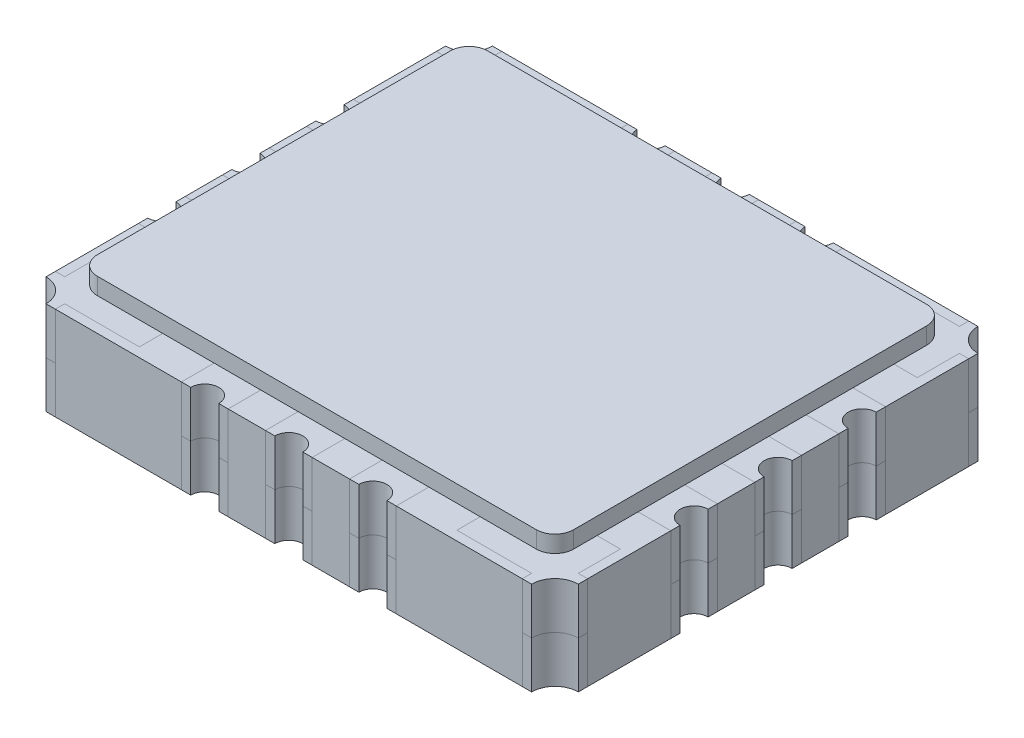
SolidWorks part; units mm, degrees
ref_plane "Спереди" through (0, 0, 0) normal (0, 0, 1) x (1, 0, 0)
ref_plane "Сверху" through (0, 0, 0) normal (0, 1, 0) x (1, 0, 0)
ref_plane "Справа" through (0, 0, 0) normal (1, 0, 0) x (0, 0, -1)
sketch "Эскиз1" plane through (0, 0, 0) normal (0, 1, 0) x (1, 0, 0)
  line L0 (0, 2.39) -> (0, -2.39) construction
  line L1 (-2.6, 2.39) -> (-1.05, 2.39)
  line L2 (-2.85, 2.14) -> (-2.85, 1.05)
  line L3 (-2.6, -2.39) -> (-1.05, -2.39)
  line L4 (2.85, 2.14) -> (2.85, 1.05)
  line L5 (-2.85, 0) -> (2.85, 0) construction
  line L6 (-2.85, -0.65) -> (-1.85, -0.65)
  line L7 (-2.85, 1.15) -> (-1.85, 1.15)
  line L8 (-2.85, 1.15) -> (-2.85, 1.05)
  line L9 (-2.85, 0.65) -> (-1.85, 0.65)
  line L10 (-1.85, 1.15) -> (-1.85, 0.65)
  line L11 (-2.85, 0.25) -> (-1.85, 0.25)
  line L12 (-2.85, 0.25) -> (-2.85, 0.15)
  line L13 (-2.85, -0.25) -> (-1.85, -0.25)
  line L14 (-1.85, 0.25) -> (-1.85, -0.25)
  line L15 (-2.85, -0.65) -> (-2.85, -0.75)
  line L16 (-2.85, -1.15) -> (-1.85, -1.15)
  line L17 (-1.85, -0.65) -> (-1.85, -1.15)
  line L18 (-0.75, -2.39) -> (-0.15, -2.39)
  line L19 (-0.75, -2.39) -> (-0.65, -2.39)
  line L20 (0.65, -2.39) -> (0.65, -1.39)
  line L21 (-1.15, -2.39) -> (-1.15, -1.39)
  line L22 (-1.15, -2.39) -> (-1.05, -2.39)
  line L23 (-0.65, -2.39) -> (-0.65, -1.39)
  line L24 (-1.15, -1.39) -> (-0.65, -1.39)
  line L25 (-0.25, -2.39) -> (-0.25, -1.39)
  line L26 (-0.25, -2.39) -> (-0.15, -2.39)
  line L27 (0.25, -2.39) -> (0.25, -1.39)
  line L28 (-0.25, -1.39) -> (0.25, -1.39)
  line L29 (0.65, -2.39) -> (0.75, -2.39)
  line L30 (1.15, -2.39) -> (1.15, -1.39)
  line L31 (0.65, -1.39) -> (1.15, -1.39)
  line L32 (0.15, -2.39) -> (0.75, -2.39)
  line L33 (0.15, -2.39) -> (0.25, -2.39)
  line L34 (1.05, -2.39) -> (1.15, -2.39)
  line L35 (1.05, -2.39) -> (2.6, -2.39)
  line L36 (-2.85, 0.75) -> (-2.85, 0.15)
  line L37 (-2.85, 0.75) -> (-2.85, 0.65)
  line L38 (-2.85, -0.15) -> (-2.85, -0.25)
  line L39 (-2.85, -0.15) -> (-2.85, -0.75)
  line L40 (-2.85, -1.05) -> (-2.85, -1.15)
  line L41 (-2.85, -1.05) -> (-2.85, -2.14)
  line L42 (-2.85, 0.75) -> (-2.85, 0.25)
  line L43 (-2.85, 0.25) -> (-2.8423, 0.2575)
  line L44 (2.85, 0.25) -> (2.8423, 0.2575)
  line L45 (2.85, 0.75) -> (2.85, 0.25)
  line L46 (2.85, -1.05) -> (2.85, -1.15)
  line L47 (2.85, -0.15) -> (2.85, -0.75)
  line L48 (2.85, -0.15) -> (2.85, -0.25)
  line L49 (2.85, 0.75) -> (2.85, 0.65)
  line L50 (2.85, 0.75) -> (2.85, 0.15)
  line L51 (1.85, -0.65) -> (1.85, -1.15)
  line L52 (2.85, -1.15) -> (1.85, -1.15)
  line L53 (2.85, -0.65) -> (2.85, -0.75)
  line L54 (1.85, 0.25) -> (1.85, -0.25)
  line L55 (2.85, -0.25) -> (1.85, -0.25)
  line L56 (2.85, 0.25) -> (2.85, 0.15)
  line L57 (2.85, 0.25) -> (1.85, 0.25)
  line L58 (1.85, 1.15) -> (1.85, 0.65)
  line L59 (2.85, 0.65) -> (1.85, 0.65)
  line L60 (2.85, 1.15) -> (2.85, 1.05)
  line L61 (2.85, 1.15) -> (1.85, 1.15)
  line L62 (2.85, -0.65) -> (1.85, -0.65)
  line L63 (1.05, 2.39) -> (1.15, 2.39)
  line L64 (0.15, 2.39) -> (0.25, 2.39)
  line L65 (0.15, 2.39) -> (0.75, 2.39)
  line L66 (0.65, 1.39) -> (1.15, 1.39)
  line L67 (1.15, 2.39) -> (1.15, 1.39)
  line L68 (0.65, 2.39) -> (0.75, 2.39)
  line L69 (-0.25, 1.39) -> (0.25, 1.39)
  line L70 (0.25, 2.39) -> (0.25, 1.39)
  line L71 (-0.25, 2.39) -> (-0.15, 2.39)
  line L72 (-0.25, 2.39) -> (-0.25, 1.39)
  line L73 (-1.15, 1.39) -> (-0.65, 1.39)
  line L74 (-0.65, 2.39) -> (-0.65, 1.39)
  line L75 (-1.15, 2.39) -> (-1.05, 2.39)
  line L76 (-1.15, 2.39) -> (-1.15, 1.39)
  line L77 (0.65, 2.39) -> (0.65, 1.39)
  line L78 (-0.75, 2.39) -> (-0.65, 2.39)
  line L79 (-0.75, 2.39) -> (-0.15, 2.39)
  line L80 (-2.5, 2.39) -> (-2.5, 2.29)
  line L81 (-2.5, 2.29) -> (-1.7, 2.29)
  line L82 (-2.75, 2.04) -> (-2.75, 1.59)
  line L83 (-2.75, 1.59) -> (-1.7, 1.59)
  line L84 (-1.7, 2.29) -> (-1.7, 1.59)
  line L85 (-2.85, 2.04) -> (-2.75, 2.04)
  line L86 (2.85, 2.04) -> (2.75, 2.04)
  line L87 (1.7, 2.29) -> (1.7, 1.59)
  line L88 (2.75, 1.59) -> (1.7, 1.59)
  line L89 (2.75, 2.04) -> (2.75, 1.59)
  line L90 (2.5, 2.29) -> (1.7, 2.29)
  line L91 (2.5, 2.39) -> (2.5, 2.29)
  line L92 (2.5, -2.39) -> (2.5, -2.29)
  line L93 (2.5, -2.29) -> (1.7, -2.29)
  line L94 (2.75, -2.04) -> (2.75, -1.59)
  line L95 (2.75, -1.59) -> (1.7, -1.59)
  line L96 (1.7, -2.29) -> (1.7, -1.59)
  line L97 (2.85, -2.04) -> (2.75, -2.04)
  line L98 (-2.85, -2.04) -> (-2.75, -2.04)
  line L99 (-1.7, -2.29) -> (-1.7, -1.59)
  line L100 (-2.75, -1.59) -> (-1.7, -1.59)
  line L101 (-2.75, -2.04) -> (-2.75, -1.59)
  line L102 (-2.5, -2.29) -> (-1.7, -2.29)
  line L103 (-2.5, -2.39) -> (-2.5, -2.29)
  line L104 (2.85, -1.05) -> (2.85, -2.14)
  line L105 (2.85, -0.15) -> (2.85, -0.75)
  line L106 (2.85, 0.75) -> (2.85, 0.15)
  line L107 (1.05, 2.39) -> (2.6, 2.39)
  line L108 (0.15, 2.39) -> (0.75, 2.39)
  line L109 (-0.75, 2.39) -> (-0.15, 2.39)
  line L110 (-0.935, 0.7229) -> (-0.7229, 0.935)
  line L111 (-0.935, -0.935) -> (-0.935, 0.7229)
  line L112 (-0.935, -0.935) -> (0.935, -0.935)
  line L113 (0.935, -0.935) -> (0.935, 0.935)
  line L114 (-0.7229, 0.935) -> (0.935, 0.935)
  line L116 (-2.4, 2.14) -> (2.3, 2.14)
  line L117 (-2.6, 1.94) -> (-2.6, -1.84)
  line L118 (-2.4, -2.04) -> (2.3, -2.04)
  line L119 (2.5, 1.94) -> (2.5, -1.84)
  arc A0 (-2.85, 2.14) -> (-2.6, 2.39) centre (-2.85, 2.39) ccw
  arc A1 (2.85, 1.05) -> (2.85, 0.75) centre (2.85, 0.9) ccw
  arc A2 (2.85, 0.15) -> (2.85, -0.15) centre (2.85, 0) ccw
  arc A3 (2.85, -0.75) -> (2.85, -1.05) centre (2.85, -0.9) ccw
  arc A4 (-2.85, -0.75) -> (-2.85, -1.05) centre (-2.85, -0.9) cw
  arc A5 (-2.85, 0.15) -> (-2.85, -0.15) centre (-2.85, 0) cw
  arc A6 (-2.85, 1.05) -> (-2.85, 0.75) centre (-2.85, 0.9) cw
  arc A7 (-0.75, -2.39) -> (-1.05, -2.39) centre (-0.9, -2.39) ccw
  arc A8 (0.15, -2.39) -> (-0.15, -2.39) centre (0, -2.39) ccw
  arc A9 (1.05, -2.39) -> (0.75, -2.39) centre (0.9, -2.39) ccw
  arc A10 (1.05, 2.39) -> (0.75, 2.39) centre (0.9, 2.39) cw
  arc A11 (0.15, 2.39) -> (-0.15, 2.39) centre (0, 2.39) cw
  arc A12 (-0.75, 2.39) -> (-1.05, 2.39) centre (-0.9, 2.39) cw
  arc A13 (2.85, 2.14) -> (2.6, 2.39) centre (2.85, 2.39) cw
  arc A14 (2.85, -2.14) -> (2.6, -2.39) centre (2.85, -2.39) ccw
  arc A15 (-2.85, -2.14) -> (-2.6, -2.39) centre (-2.85, -2.39) cw
  arc A16 (-2.6, -1.84) -> (-2.4, -2.04) centre (-2.4, -1.84) ccw
  arc A17 (2.5, 1.94) -> (2.3, 2.14) centre (2.3, 1.94) ccw
  arc A18 (2.5, -1.84) -> (2.3, -2.04) centre (2.3, -1.84) cw
  arc A19 (-2.4, 2.14) -> (-2.6, 1.94) centre (-2.4, 1.94) ccw
  point P9 (-2.85, 2.14)
  point P11 (-2.6, 2.39)
  point P27 (-1.85, 0.9)
  point P28 (-1.85, -0.9)
  point P50 (-0.9, -1.39)
  point P51 (0.9, -1.39)
  point P79 (1.85, -0.9)
  point P80 (1.85, 0.9)
  point P101 (0.9, 1.39)
  point P102 (-0.9, 1.39)
  point P141 (-0.935, 0)
  point P142 (0, 0.935)
  dimension "D8" = 1.05
  dimension "D13" = 0.1
  dimension "D11" = 0.7
  dimension "D16" = 0.25
  dimension "D19" = 0.2
  dimension "D20" = 0.2
  dimension "D2" = 5.7
  dimension "D3" = 4.78
  dimension "D4" = 0.5
  dimension "D5" = 1
  dimension "D6" = 1.8
  dimension "D7" = 0.9
  dimension "D9" = 1.8
  dimension "D10" = 0.9
  dimension "D12" = 0.1
  dimension "D14" = 0.1
  dimension "D15" = 0.1
  dimension "D17" = 1.87
  dimension "D18" = 0.3
extrude "Бобышка-Вытянуть7" add sketch "Эскиз1" along normal blind 0.5 contours A16 L117 L100 L101 L98 L41 A15 L3 L103 L102 L99 L118 | L117 A16 L118 L99 L100 | L6 L117 L16 L17 | L15 A4 L40 L16 L117 L6 | L11 L117 L13 L14 | L12 A5 L38 L13 L117 L11 | L7 L117 L9 L10 | L2 A6 L36 L9 L117 L7 | L116 A19 L117 L83 L84 | A19 L116 L84 L81 L80 L1 A0 L2 L85 L82 L83 L117 | L116 L76 L73 L74 | L78 A12 L1 L76 L116 L74 | L116 L72 L69 L70 | L64 A11 L71 L72 L116 L70 | L116 L77 L66 L67 | L63 A10 L65 L77 L116 L67 | L119 A17 L116 L87 L88 | A17 L119 L88 L89 L86 L4 A13 L107 L91 L90 L87 L116 | A1 L4 L61 L119 L59 L45 | L119 L61 L58 L59 | A2 L50 L57 L119 L55 L47 | L119 L57 L54 L55 | A3 L47 L62 L119 L52 L46 | L119 L62 L51 L52 | L119 A18 L118 L96 L93 L92 L35 A14 L104 L97 L94 L95 | A18 L119 L95 L96 L118 | A9 L34 L30 L118 L20 L29 | L20 L118 L30 L31 | A8 L32 L27 L118 L25 L18 | L25 L118 L27 L28 | L21 L118 L23 L24 | A7 L18 L23 L118 L21 L3 | L114 L110 L111 L112 L113 region at (-2.55, 0, -2.376) region at (-1.1, 0, -2.3844) region at (-0.9, 0, -1.765) region at (-2.725, 0, -1.1444) region at (-2.1428, 0, -1.8609) region at (-2.225, 0, -0.9) region at (0, 0, -1.765) region at (-0.2444, 0, -2.265) region at (-2.6056, 0, 0) region at (-2.225, 0, 0) region at (0.9, 0, -1.765) region at (0.6556, 0, -2.265) region at (-2.6056, 0, 0.9) region at (-2.225, 0, 0.9) region at (2.0929, 0, -1.8604) region at (1.714, 0, -2.215) region at (-2.3333, 0, 2.0941) region at (-2.1412, 0, 1.8111) region at (2.175, 0, -0.9) region at (2.6468, 0, -0.9) region at (-0.9, 0, 2.1868) region at (-0.9, 0, 1.715) region at (2.175, 0, 0) region at (2.6468, 0, 0) region at (0, 0, 2.1868) region at (0, 0, 1.715) region at (2.175, 0, 0.9) region at (2.6468, 0, 0.9) region at (0.9, 0, 2.1868) region at (0.9, 0, 1.715) region at (2.0913, 0, 1.8106) region at (2.3559, 0, 2.0622) region at (0.0056, 0, 0.0056)
extrude "Бобышка-Вытянуть10" add sketch "Эскиз1<13>" along normal blind 1 separate body contours L119 L88 L87 L116 L67 L66 L77 L70 L69 L72 L74 L73 L76 L84 L83 L117 L7 L10 L9 L11 L14 L13 L6 L17 L16 L100 L99 L118 L21 L24 L23 L25 L28 L27 L20 L31 L30 L96 L95 L52 L51 | L67 L116 L87 L90 L91 L107 | L88 L119 L61 L4 L86 L89 | L70 L116 L77 L65 | L74 L116 L72 L79 | L84 L116 L76 L1 L80 L81 | L117 L83 L82 L85 L2 L7 | L117 L9 L36 L11 | L117 L13 L39 L6 | L117 L16 L41 L98 L101 L100 | L118 L99 L102 L103 L3 L21 | L118 L23 L18 L25 | L118 L27 L32 L20 | L118 L30 L35 L92 L93 L96 | L52 L119 L95 L94 L97 L104 | L55 L119 L62 L47 | L59 L119 L57 L45 region at (-1.6733, 0, -2.2926) region at (-2.7468, 0, -1.4992) region at (-1.2159, 0, -1.765) region at (-0.45, 0, -2.265) region at (-2.725, 0, -0.45) region at (0.45, 0, -2.265) region at (-2.725, 0, 0.45) region at (1.6733, 0, -2.2926) region at (-2.7468, 0, 1.4992) region at (2.7033, 0, -1.4706) region at (-1.6232, 0, 2.2517) region at (2.675, 0, -0.45) region at (-0.45, 0, 2.215) region at (2.675, 0, 0.45) region at (0.45, 0, 2.215) region at (2.7033, 0, 1.4706) region at (1.6232, 0, 2.2517)
sketch "Эскиз1<13>" plane through (0, 0, 0) normal (0, 1, 0) x (1, 0, 0) same geometry as "Эскиз1"
extrude "Бобышка-Вытянуть11" add sketch "Эскиз1<14>" along normal blind 0.5 from offset 0.5 separate body contours A19 L116 L84 L81 L80 L1 A0 L2 L85 L82 L83 L117 | L116 A19 L117 L83 L84 | L7 L117 L9 L10 | L2 A6 L36 L9 L117 L7 | L12 A5 L38 L13 L117 L11 | L11 L117 L13 L14 | L15 A4 L40 L16 L117 L6 | L6 L117 L16 L17 | A16 L117 L100 L101 L98 L41 A15 L3 L103 L102 L99 L118 | L117 A16 L118 L99 L100 | A7 L18 L23 L118 L21 L3 | A8 L32 L27 L118 L25 L18 | A9 L34 L30 L118 L20 L29 | L119 A18 L118 L96 L93 L92 L35 A14 L104 L97 L94 L95 | A3 L47 L62 L119 L52 L46 | A2 L50 L57 L119 L55 L47 | A1 L4 L61 L119 L59 L45 | A17 L119 L88 L89 L86 L4 A13 L107 L91 L90 L87 L116 | L63 A10 L65 L77 L116 L67 | L64 A11 L71 L72 L116 L70 | L78 A12 L1 L76 L116 L74 | L116 L76 L73 L74 | L116 L72 L69 L70 | L116 L77 L66 L67 | L119 A17 L116 L87 L88 | L119 L61 L58 L59 | L119 L57 L54 L55 | L119 L62 L51 L52 | A18 L119 L95 L96 L118 | L20 L118 L30 L31 | L25 L118 L27 L28 | L21 L118 L23 L24 | L114 L110 L111 L112 L113 region at (-2.55, 0, -2.376) region at (-1.1, 0, -2.3844) region at (-0.9, 0, -1.765) region at (-2.725, 0, -1.1444) region at (-2.1428, 0, -1.8609) region at (-2.225, 0, -0.9) region at (0, 0, -1.765) region at (-0.2444, 0, -2.265) region at (-2.6056, 0, 0) region at (-2.225, 0, 0) region at (0.9, 0, -1.765) region at (0.6556, 0, -2.265) region at (-2.6056, 0, 0.9) region at (-2.225, 0, 0.9) region at (2.0929, 0, -1.8604) region at (1.714, 0, -2.215) region at (-2.3333, 0, 2.0941) region at (-2.1412, 0, 1.8111) region at (2.175, 0, -0.9) region at (2.6468, 0, -0.9) region at (-0.9, 0, 2.1868) region at (-0.9, 0, 1.715) region at (2.175, 0, 0) region at (2.6468, 0, 0) region at (0, 0, 2.1868) region at (0, 0, 1.715) region at (2.175, 0, 0.9) region at (2.6468, 0, 0.9) region at (0.9, 0, 2.1868) region at (0.9, 0, 1.715) region at (2.0913, 0, 1.8106) region at (2.3559, 0, 2.0622) region at (0.0056, 0, 0.0056)
sketch "Эскиз1<14>" plane through (0, 0, 0) normal (0, 1, 0) x (1, 0, 0) same geometry as "Эскиз1"
extrude "Бобышка-Вытянуть13" add sketch "Эскиз1<16>" along normal blind 1.18 separate body contours L118 A18 L119 A17 L116 A19 L117 A16
sketch "Эскиз1<16>" plane through (0, 0, 0) normal (0, 1, 0) x (1, 0, 0) same geometry as "Эскиз1"
